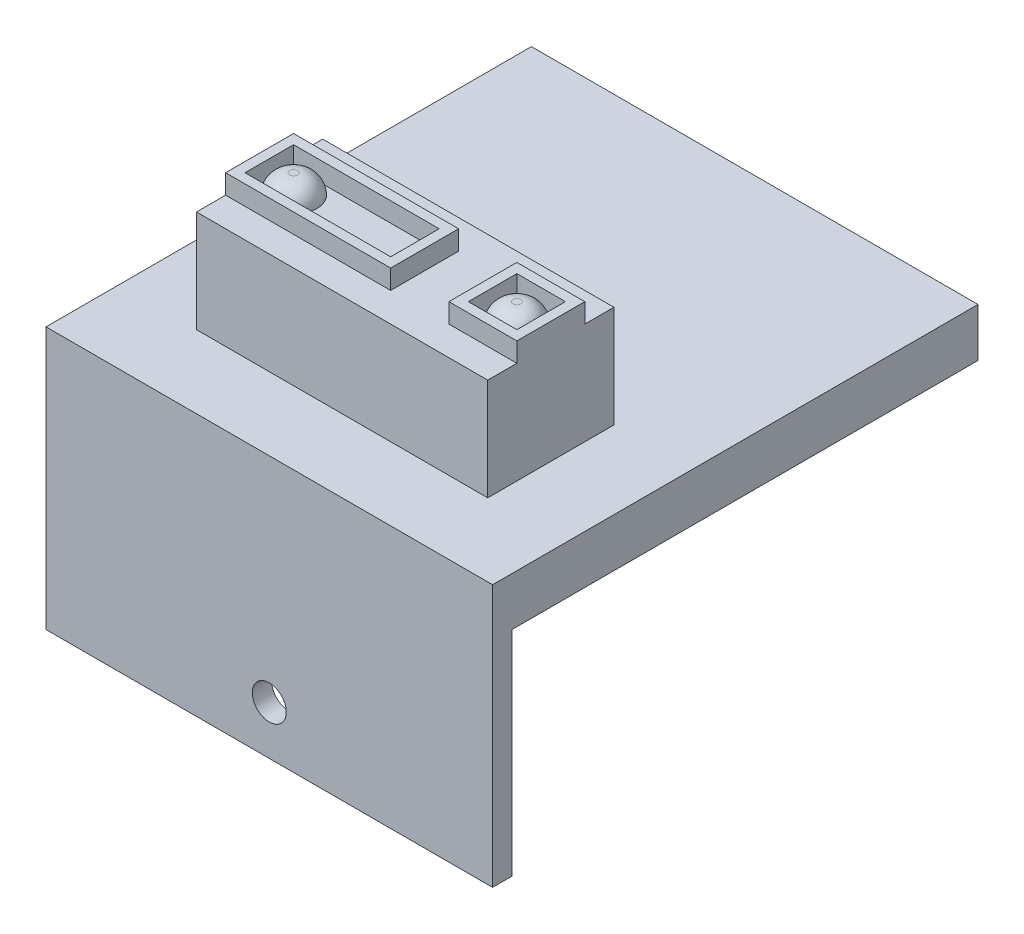
SolidWorks part; units mm, degrees
ref_plane "Front Plane" through (0, 0, 0) normal (0, 0, 1) x (1, 0, 0)
ref_plane "Top Plane" through (0, 0, 0) normal (0, 1, 0) x (1, 0, 0)
ref_plane "Right Plane" through (0, 0, 0) normal (1, 0, 0) x (0, 0, -1)
sketch "Sketch1" plane through (0, 0, 0) normal (0, 1, 0) x (1, 0, 0)
  line L1 (0, 0) -> (46, 0)
  line L2 (0, 0) -> (0, 50)
  line L3 (0, 50) -> (46, 50)
  line L4 (46, 0) -> (46, 50)
  dimension "D1" = 50
  dimension "D2" = 46
extrude "Boss-Extrude1" add sketch "Sketch1" along normal blind 5
sketch "Sketch2" plane through (0, 5, 0) normal (0, 1, 0) x (1, 0, 0)
  line L0 (23, 50) -> (23, 0) construction
  line L1 (8, 7.5) -> (38, 7.5)
  line L2 (8, 7.5) -> (8, 20.5)
  line L3 (8, 20.5) -> (38, 20.5)
  line L4 (38, 7.5) -> (38, 20.5)
  line L5 (46, 50) -> (0, 50) construction
  line L6 (0, 0) -> (46, 0) construction
  dimension "D1" = 13
  dimension "D2" = 30
  dimension "D3" = 7.5
extrude "Boss-Extrude2" add sketch "Sketch2" along normal blind 12.5
sketch "Sketch3" plane through (0, 0, 0) normal (0, -1, 0) x (1, 0, 0)
  line L0 (0, -50) -> (0, 0) construction
  line L1 (46, 0) -> (0, 0)
  line L2 (46, 0) -> (46, -2)
  line L3 (46, -2) -> (0, -2)
  line L4 (0, 0) -> (0, -2)
  dimension "D1" = 2
extrude "Boss-Extrude3" add sketch "Sketch3" along normal blind 22
sketch "Sketch4" plane through (0, 0, -2) normal (0, 0, -1) x (-1, 0, 0)
  line L0 (-23, -22) -> (-23, 0) construction
  line L1 (0, -22) -> (-46, -22) construction
  line L2 (0, 0) -> (-46, 0) construction
  circle A0 centre (-23, -17) radius 1.75
  dimension "D1" = 3.5
  dimension "D2" = 5
extrude "Cut-Extrude1" cut sketch "Sketch4" against normal blind 22
sketch "Sketch5" plane through (0, 17.5, 0) normal (0, 1, 0) x (1, 0, 0)
  line L0 (38, 7.5) -> (38, 20.5) construction
  line L1 (9, 16.5) -> (24, 16.5)
  line L2 (9, 16.5) -> (9, 11.5)
  line L3 (9, 11.5) -> (24, 11.5)
  line L4 (24, 16.5) -> (24, 11.5)
  line L5 (37, 16.5) -> (32, 16.5)
  line L6 (37, 16.5) -> (37, 11.5)
  line L7 (37, 11.5) -> (32, 11.5)
  line L8 (32, 16.5) -> (32, 11.5)
  line L10 (31, 17.5) -> (31, 10.5)
  line L12 (25, 17.5) -> (25, 10.5)
  line L13 (8, 20.5) -> (8, 7.5) construction
  line L14 (31, 17.5) -> (38, 17.5)
  line L15 (8, 20.5) -> (38, 20.5)
  line L16 (8, 20.5) -> (8, 17.5)
  line L17 (8, 17.5) -> (25, 17.5)
  line L18 (38, 20.5) -> (38, 17.5)
  line L19 (8, 7.5) -> (38, 7.5)
  line L20 (8, 7.5) -> (8, 10.5)
  line L21 (8, 10.5) -> (25, 10.5)
  line L22 (38, 7.5) -> (38, 10.5)
  line L23 (31, 10.5) -> (38, 10.5)
  dimension "D1" = 1
  dimension "D2" = 1
  dimension "D3" = 1
  dimension "D4" = 1
  dimension "D5" = 15
  dimension "D6" = 5
  dimension "D7" = 5
  dimension "D8" = 3
  dimension "D9" = 3
  dimension "D10" = 1
extrude "Cut-Extrude2" cut sketch "Sketch5" against normal blind 2
sketch "Sketch6" plane through (0, 15.5, 0) normal (0, 1, 0) x (1, 0, 0)
  line L0 (32, 16.5) -> (37, 11.5) construction
  line L1 (32, 16.5) -> (32, 11.5) construction
  line L2 (37, 16.5) -> (32, 16.5) construction
  line L3 (9, 16.5) -> (14, 11.5) construction
  line L4 (9, 11.5) -> (24, 11.5) construction
  line L6 (9, 16.5) -> (9, 11.5) construction
  circle A0 centre (11.5, 14) radius 2.4
  circle A1 centre (34.5, 14) radius 2.4
  dimension "D1" = 4.8
  dimension "D2" = 4.8
  dimension "D3" = 2.5
extrude "Boss-Extrude6" add sketch "Sketch6" along normal blind 2
fillet "Fillet1" radius 2 2 edges at (34.5, 17.5, -11.6) (11.5, 17.5, -11.6)
